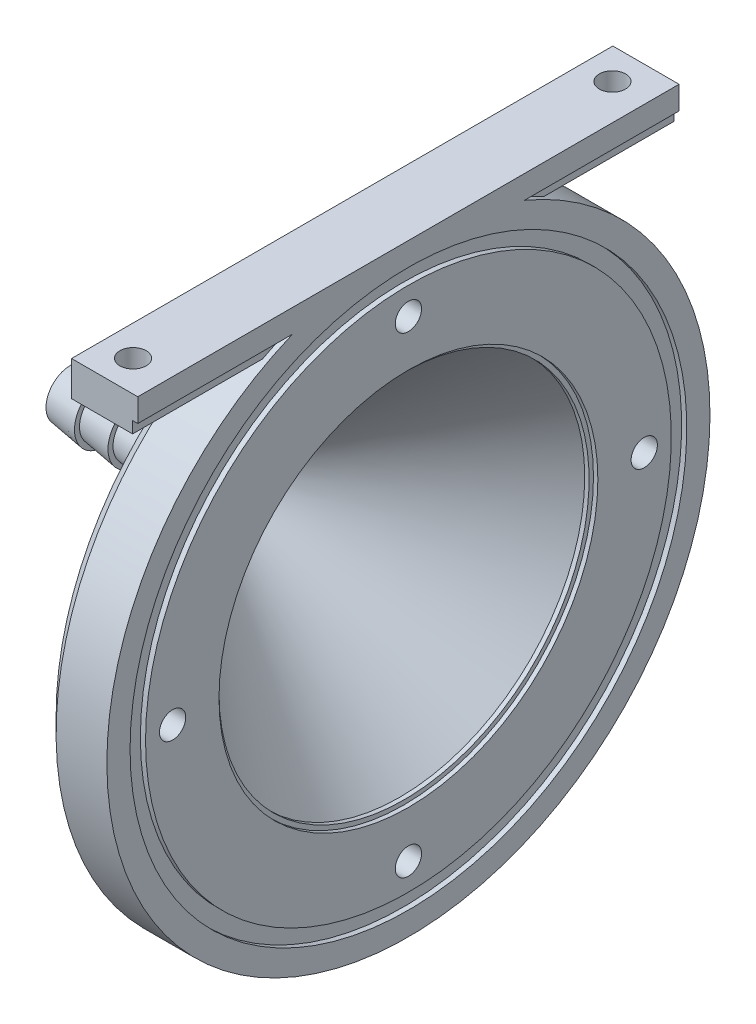
SolidWorks part; units mm, degrees
ref_plane "Front Plane" through (0, 0, 0) normal (0, 0, 1) x (1, 0, 0)
ref_plane "Top Plane" through (0, 0, 0) normal (0, 1, 0) x (1, 0, 0)
ref_plane "Right Plane" through (0, 0, 0) normal (1, 0, 0) x (0, 0, -1)
sketch "Sketch1" plane through (0, 0, 0) normal (0, 0, 1) x (1, 0, 0)
  line L0 (-801.9271, 0) -> (36107.5217, 0) construction
  line L3 (-14.0102, 3.8) -> (-14.0102, 3.15)
  line L8 (-18.3435, 1.9) -> (0, 1.9)
  line L9 (-18.3435, 1.9) -> (-18.3435, 3.15)
  line L10 (25.3752, 24.5) -> (25.3752, 39)
  line L12 (25.3752, 39) -> (16.8092, 39)
  line L16 (25.3752, 24.5) -> (24.8092, 24.5)
  line L17 (24.8092, 24.5) -> (24.8092, 23.934)
  line L18 (16.8092, 39) -> (16.8092, 23.934)
  line L20 (0, 1.9) -> (24.2432, 23.934)
  line L21 (-18.3435, 3.15) -> (-14.0102, 3.8)
  line L22 (24.2432, 23.934) -> (24.8092, 23.934)
  line L23 (-14.0102, 3.15) -> (-9.6768, 3.8)
  line L25 (-9.6768, 3.15) -> (-5.3435, 3.8)
  line L26 (-9.6768, 3.8) -> (-9.6768, 3.15)
  line L27 (-5.3435, 3.8) -> (16.8092, 23.934)
  line L28 (16.8092, 34.5) -> (25.3752, 34.5)
  line L36 (16.8092, 39) -> (25.3752, 39)
  line L38 (25.3752, 36) -> (24.7082, 36)
  line L39 (24.7082, 36) -> (24.7082, 34)
  line L40 (24.7082, 34) -> (25.3752, 34)
  dimension "D3" = 0.566
  dimension "D2" = 7.6
  dimension "D6" = 3.8
  dimension "D7" = 6.3
  dimension "D5" = 39
  dimension "D8" = 24.5
  dimension "D10" = 0.566
  dimension "D4" = 5
  dimension "D9" = 0.566
  dimension "D11" = 13
  dimension "D12" = 8.566
  dimension "D13" = 4.5
  dimension "D17" = 36
  dimension "D18" = 2
  dimension "D19" = 0.667
revolve "Revolve17" add sketch "Sketch1" angle 360 about L0 region at (11.1774, 17.6055, 0) region at (20.9869, 36.79, 0)
sketch "Sketch4" plane through (16.8092, 0, 0) normal (-1, 0, 0) x (0, 0, 1)
  circle A0 centre (0, 0) radius 30.5 construction
  circle A2 centre (0, 0) radius 39 construction
  point P3 (0, 30.5)
  point P7 (30.5, 0)
  point P12 (-30.5, 0)
  point P13 (0, -30.5)
  point P22 (0, 0)
  point P23 (0, 31.75)
  point P24 (0, 31.4392)
  point P27 (0, -30.5)
  dimension "D1" = 8.5
hole_wizard "M3 Clearance Hole1" positions "Sketch4" profile "Sketch5" hole size "M3" standard "ISO"
sketch "Sketch5" plane through (16.8092, -30.5, 0) normal (0, 1, 0) x (0, 0, 1)
  line L0 (0, 0) -> (0, 9.5875)
  line L1 (0, 9.5875) -> (1.7, 8.566)
  line L2 (1.7, 8.566) -> (1.7, 0)
  line L5 (1.7, 0) -> (0, 0)
  line L10 (0, 9.5875) -> (-1.7, 8.566) construction
  line L11 (0, -6.35) -> (0, 107.95) construction
  dimension "Hole Dia." = 3.4
  dimension "Hole Depth" = 8.566
  dimension "Drill Angle" = 118
chamfer "Chamfer1" distance 2 angle 45 1 edges at (16.8092, 0, 39)
extrude "Boss-Extrude1" add sketch "Sketch1<11>" against normal mid plane 70 contours L18 L28 L10 L12 region at (20.9869, 36.79, 0)
sketch "Sketch1<11>" plane through (0, 0, 0) normal (0, 0, 1) x (1, 0, 0) same geometry as "Sketch1"
sketch "Sketch9" plane through (0, 34.5, 0) normal (0, -1, 0) x (-1, 0, 0)
  line L0 (-16.8092, -35) -> (-25.3752, 35) construction
  line L1 (-16.8092, -13.3697) -> (-16.8092, -35) construction
  line L2 (-16.8092, -35) -> (-24.7082, -35) construction
  line L3 (-25.3752, 35) -> (-25.3752, -18.1865) construction
  line L4 (-25.3752, 35) -> (-16.1422, 35) construction
  line L5 (-16.8092, 35) -> (-24.7082, 35) construction
  line L6 (-16.1422, 35) -> (-25.3752, -35) construction
  line L7 (-25.3752, -18.1865) -> (-25.3752, -35) construction
  line L8 (-20.7587, -35) -> (-20.7587, 35) construction
  line L9 (-4.5963, 0) -> (-25.3752, 0) construction
  line L10 (-25.3752, 39) -> (-25.3752, -39) construction
  circle A0 centre (-20.7587, -31) radius 1.7
  circle A1 centre (-20.7587, 31) radius 1.7
  dimension "D1" = 3.4
  dimension "D2" = 4
extrude "Cut-Extrude1" cut sketch "Sketch9" against normal blind 10
sketch "Sketch10" plane through (16.8092, 0, 0) normal (-1, 0, 0) x (0, 0, 1)
  line L0 (37, 0) -> (23.934, 0)
  line L1 (-23.934, 0) -> (-37, 0)
  line L2 (0, -23.934) -> (0, -37)
  circle A1 centre (0, 0) radius 23.934 construction
  point P15 (0, 30.467)
equation "\"D10@Sketch1\"=\"D3@Sketch1\""
equation "\"D9@Sketch1\"=\"D3@Sketch1\""
